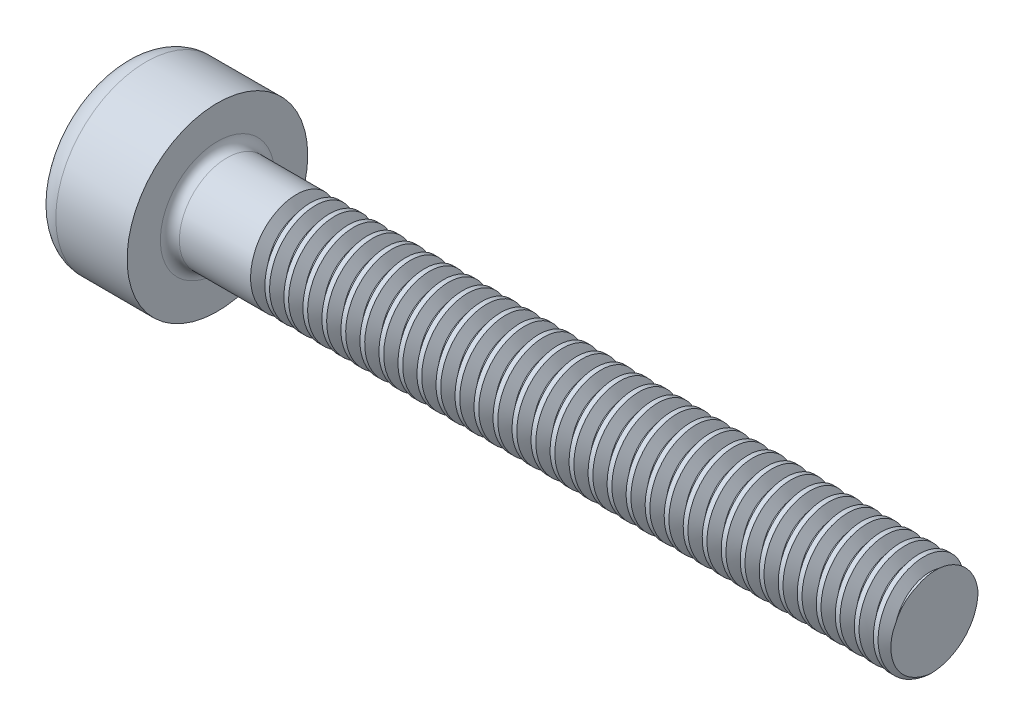
SolidWorks part; units mm, degrees
ref_plane "Спереди" through (0, 0, 0) normal (0, 0, 1) x (1, 0, 0)
ref_plane "Сверху" through (0, 0, 0) normal (0, 1, 0) x (1, 0, 0)
ref_plane "Справа" through (0, 0, 0) normal (1, 0, 0) x (0, 0, -1)
sketch "Эскиз1" plane through (0, 0, 0) normal (0, 0, 1) x (1, 0, 0)
  line L0 (22.1989, 0) -> (17, 0) construction
  line L1 (0, 16.1035) -> (0, -19.7496) construction
  line L2 (0, 0) -> (17, 0)
  line L3 (0, 0) -> (0, 1.9)
  line L4 (0, 1.9) -> (2, 1.9)
  line L5 (2, 1.9) -> (2, 1)
  line L6 (2, 1) -> (17, 1)
  line L7 (17, 1) -> (17, 0)
  dimension "D1" = 3.8
  dimension "D2" = 2
  dimension "D3" = 15
  dimension "D4" = 2
revolve "Повернуть1" add sketch "Эскиз1" angle 360 about L0
thread "Резьба1" pitch 0.4 method cut profile "Профиль резьбы2" start angle 0, offset 1.5, length 0, pitch 0.4, diameter 2
ref_plane "Плоскость2" through (3.5, 0, -1) normal (0, 1, 0) x (0, 0, 1)
sketch "Профиль резьбы2" plane through (3.5, 0, -1) normal (0, 1, 0) x (0, 0, 1)
  line L0 (0, 0) -> (0, 0.4) construction
  line L1 (0, 0) -> (0.2165, 0.125)
  line L2 (0.2165, 0.125) -> (0.2165, 0.175)
  line L3 (0.2165, 0.175) -> (0, 0.3)
  line L4 (0.2165, 0.15) -> (0, 0.15) construction
  line L11 (0, 0) -> (0, 0.3)
  point P2 (0, 0)
  dimension "Pitch" = 0.4
  dimension "Profile_Angle" = 60
  dimension "Profile_Land" = 0.05
  dimension "Profile_Height" = 0.2165
sketch "Эскиз6" plane through (0, 0, 0) normal (-1, 0, 0) x (0, 0, 1)
  line L0 (0, 0) -> (-5.0338, 0) construction
  line L1 (0, 0) -> (0, 5.5177) construction
  line L3 (-0.75, 0) -> (-0.375, -0.6495)
  line L4 (-0.375, -0.6495) -> (0.375, -0.6495)
  line L5 (0.375, -0.6495) -> (0.75, 0)
  line L6 (0.75, 0) -> (0.375, 0.6495)
  line L7 (0.375, 0.6495) -> (-0.375, 0.6495)
  line L8 (-0.375, 0.6495) -> (-0.75, 0)
  dimension "D1" = 1.299
  dimension "D2" = 1.5
extrude "Вырез-Вытянуть1" cut sketch "Эскиз6" against normal blind 1 contours L3 L4 L5 L6 L7 L8
extrude "Вырез-Вытянуть2" cut sketch "Эскиз6<3>" against normal blind 2 draft 60 from offset 1 offset against normal yes
sketch "Эскиз6<3>" plane through (0, 0, 0) normal (-1, 0, 0) x (0, 0, 1) same geometry as "Эскиз6"
fillet "Скругление2" radius 0.5 1 edges at (0, 0, -1.9)
fillet "Скругление3" radius 0.2 1 edges at (2, 0, -1)
